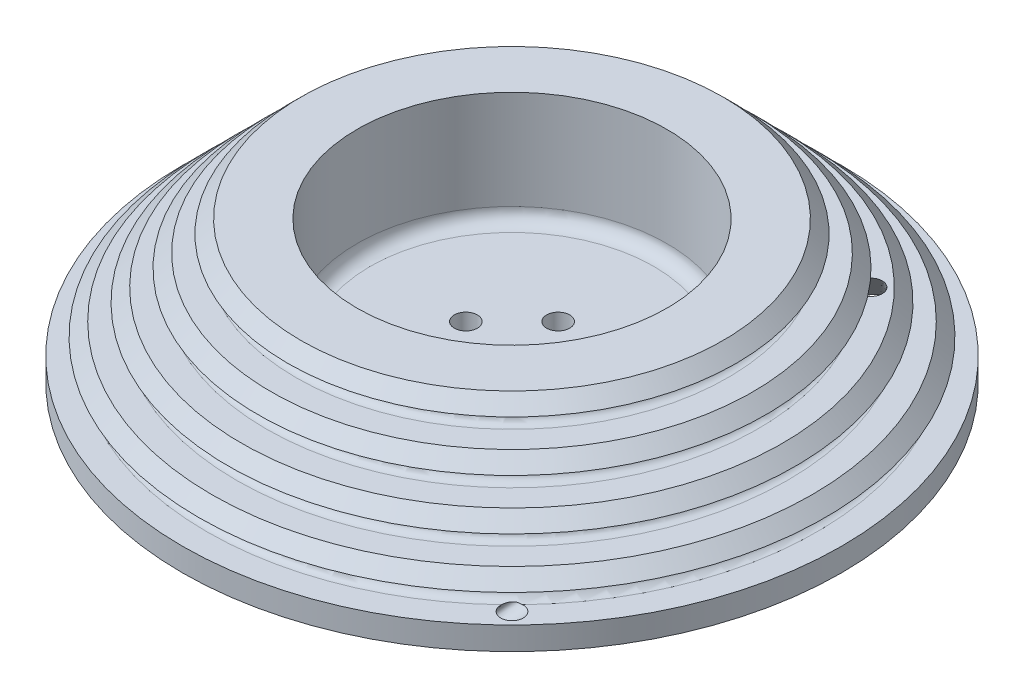
SolidWorks part; units mm, degrees
ref_plane "Front Plane" through (0, 0, 0) normal (0, 0, 1) x (1, 0, 0)
ref_plane "Top Plane" through (0, 0, 0) normal (0, 1, 0) x (1, 0, 0)
ref_plane "Right Plane" through (0, 0, 0) normal (1, 0, 0) x (0, 0, -1)
sketch "Sketch1" plane through (0, 0, 0) normal (0, 0, 1) x (1, 0, 0)
  line L0 (0, 0) -> (0, 21)
  line L1 (0, 21) -> (-32, 21)
  line L2 (-32, 21) -> (-50, 3)
  line L3 (-50, 3) -> (-50, 0)
  line L4 (-50, 0) -> (0, 0)
  dimension "D1" = 50
  dimension "D2" = 21
  dimension "D3" = 135
  dimension "D4" = 3
revolve "Revolve1" add sketch "Sketch1" angle 360 about L0
sketch "Sketch2" plane through (0, 0, 0) normal (0, 0, 1) x (1, 0, 0)
  line L0 (0, 0) -> (0, 23.1188)
  line L1 (-32, 21) -> (-50, 3) construction
  line L2 (-36.5, 19) -> (-31.5, 19)
  line L3 (-36.5, 19) -> (-36.5, 16.5)
  line L4 (-36.5, 16.5) -> (-31.5, 16.5)
  line L5 (-31.5, 19) -> (-31.5, 16.5)
  line L6 (-50, 5.5) -> (-45, 5.5)
  line L7 (-50, 5.5) -> (-50, 3)
  line L8 (-50, 3) -> (-45, 3)
  line L9 (-45, 5.5) -> (-45, 3)
  line L10 (-32, 21) -> (-50, 3)
  line L12 (32, 21) -> (-32, 21) construction
  line L13 (50, 3) -> (-50, 3) construction
  line L15 (-41, 14.5) -> (-36, 14.5)
  line L16 (-41, 14.5) -> (-41, 12)
  line L17 (-41, 12) -> (-36, 12)
  line L18 (-36, 14.5) -> (-36, 12)
  line L19 (-45.5, 10) -> (-40.5, 10)
  line L20 (-45.5, 10) -> (-45.5, 7.5)
  line L21 (-45.5, 7.5) -> (-40.5, 7.5)
  line L22 (-40.5, 10) -> (-40.5, 7.5)
  point P19 (-38.5, 14.5)
  point P26 (-43, 10)
  point P27 (-47.5, 5.5)
  point P28 (-34, 19)
  dimension "D1" = 2.5
  dimension "D2" = 2.5
  dimension "D3" = 5
  dimension "D4" = 5
  dimension "D5" = 5
  dimension "D6" = 2
  dimension "D7" = 2.5
  dimension "D8" = 2
  dimension "D9" = 5
  dimension "D10" = 2.5
  dimension "D11" = 2
revolve "Cut-Revolve1" cut sketch "Sketch2" angle 360 about L0 region at (-46.9444, 4.1111, 0) region at (-42.4444, 8.6111, 0) region at (-37.9444, 13.1111, 0) region at (-33.4444, 17.6111, 0)
fillet "Fillet1" radius 1.25 8 edges at (0, 3, -45) (0, 5.5, -45) (0, 7.5, -40.5) (0, 10, -40.5) (0, 12, -36) (0, 14.5, -36) (0, 16.5, -31.5) (0, 19, -31.5)
sketch "Sketch3" plane through (0, 21, 0) normal (0, 1, 0) x (1, 0, 0)
  line L0 (0, 0) -> (44.738, 0) construction
  line L1 (0, 0) -> (32.1015, 32.1015)
  line L2 (0, 0) -> (32.1015, -32.1015)
  dimension "D1" = 45
ref_plane "top inner hole" through (0, 0, 0) normal (0.7071, 0, 0.7071) x (0.7071, 0, -0.7071)
ref_plane "bottom outer hole" through (0, 0, 0) normal (-0.7071, 0, 0.7071) x (0.7071, 0, 0.7071)
sketch "Sketch5" plane through (0, 0, 0) normal (0.7071, 0, 0.7071) x (0.7071, 0, -0.7071)
  line L0 (36.6973, 7.047) -> (34.1324, 0)
  line L1 (-50, 0) -> (50, 0) construction
  line L2 (41, 12) -> (-41, 12) construction
  line L3 (36.6973, 7.047) -> (38.8222, 12.8851)
  point P4 (38.5, 12)
  dimension "D1" = 2.5
  dimension "D2" = 70
sketch "Sketch6" plane through (0, 0, 0) normal (-0.7071, 0, 0.7071) x (0.7071, 0, 0.7071)
  line L0 (47.5, 3) -> (42.3038, 0)
  line L1 (50, 3) -> (-50, 3) construction
  line L2 (-50, 0) -> (50, 0) construction
  line L3 (47.5, 3) -> (33.9789, -4.8064)
  line L4 (47.5, 3) -> (50.8539, 4.9364)
  dimension "D1" = 2.5
  dimension "D2" = 30
sketch "Sketch11" plane through (0, 21, 0) normal (0, 1, 0) x (1, 0, 0)
  circle A0 centre (0, 0) radius 23.5
  dimension "D1" = 47
extrude "Cut-Extrude2" cut sketch "Sketch11" against normal blind 17
fillet "Fillet2" radius 2 1 edges at (0, 4, 23.5)
ref_plane "Plane1" through (0, 0, 0) normal (0, 0, -1) x (1, 0, 0)
ref_plane "Plane2" through (21.3119, -10.9699, -21.3119) normal (0.6645, -0.342, -0.6645) x (0.2418, 0.9397, -0.2418)
ref_plane "Plane3" through (7.4783, -18.3181, 7.4783) normal (-0.3536, 0.866, -0.3536) x (-0.6124, -0.5, -0.6124)
sketch "Sketch19" plane through (0, 0, 0) normal (0, -1, 0) x (1, 0, 0)
  circle A1 centre (0, 0) radius 50
  circle A2 centre (0, 0) radius 50
  dimension "D1" = 0
extrude "Boss-Extrude1" add sketch "Sketch19" along normal blind 0.5
sketch "Sketch9" plane through (0, -0.5, 0) normal (0, -1, 0) x (1, 0, 0)
  line L0 (0, 0) -> (0, 20.7323)
  line L1 (0, 0) -> (44.738, 0) construction
  circle A0 centre (0, 0) radius 7 construction
  circle A1 centre (0, 7) radius 1.75
  circle A2 centre (7, 0) radius 1.75
  circle A3 centre (0, -7) radius 1.75
  circle A4 centre (-7, 0) radius 1.75
  point P0 (0, 0)
  point P16 (0, 0)
  dimension "D1" = 14
  dimension "D2" = 3.5
  dimension "D3" = 4
extrude "Cut-Extrude1" cut sketch "Sketch9" against normal through all and the other way blind 0.5 contours A4 | L0 A1 | L0 A1 | A2 | A3 region at (-0.7427, -0.5, 7) region at (0.7427, -0.5, 7) region at (7, -0.5, 0) region at (0, -0.5, -7) region at (-7, -0.5, 0)
sketch "Sketch20" plane through (0, -0.5, 0) normal (0, -1, 0) x (1, 0, 0)
  circle A0 centre (0, 0) radius 2.6
  dimension "D1" = 5.2
extrude "Cut-Extrude3" cut sketch "Sketch20" against normal blind 3
sketch "Sketch8" plane through (0, 3, 0) normal (0, 1, 0) x (1, 0, 0)
  circle A0 centre (33.5876, -33.5876) radius 1.7
  dimension "D1" = 3.4
sketch "Sketch7" plane through (0, 12, 0) normal (0, 1, 0) x (1, 0, 0)
  circle A0 centre (27.2236, 27.2236) radius 1.7
  dimension "D1" = 3.4
sketch "Sketch22" plane through (0, 21, 0) normal (0, 1, 0) x (1, 0, 0)
  line L0 (28.4257, 28.4257) -> (51.9261, 4.9253)
  line L2 (27.2236, 27.2236) -> (28.4257, 28.4257)
  line L3 (25.9489, 25.9489) -> (27.4514, 27.4514) construction
  line L4 (34.7897, -34.7897) -> (57.5245, -12.0548)
  line L5 (33.5876, -33.5876) -> (35.9592, -35.9592) construction
  line L6 (27.2236, 27.2236) -> (28.3989, 25.9953)
  line L7 (33.5876, -33.5876) -> (34.7897, -32.3855)
  circle A0 centre (27.2236, 27.2236) radius 1.7 construction
  circle A1 centre (33.5876, -33.5876) radius 1.7 construction
  circle A2 centre (0, 0) radius 38.5 construction
ref_plane "Plane7" through (27.8112, 0, -26.6094) normal (-0.7225, 0, 0.6913) x (0.6913, 0, 0.7225)
ref_plane "Plane8" through (33.5876, 0, 33.5876) normal (0.7071, 0, 0.7071) x (0.7071, 0, -0.7071)
sketch "Sketch24" plane through (27.8112, 0, -26.6094) normal (-0.7225, 0, 0.6913) x (0.6913, 0, 0.7225)
  line L0 (-16.5385, -1.3805) -> (1.161, 13.7152)
  line L2 (-0.8102, 7.047) -> (-0.8571, 12.8851) construction
  point P2 (-14.3017, -2.5124)
  point P3 (1.1241, 13.7795)
  point P5 (-14.6316, -3.3373)
  dimension "D1" = 50
sketch "Sketch25" plane through (33.5876, 0, 33.5876) normal (0.7071, 0, 0.7071) x (0.7071, 0, -0.7071)
  line L0 (1.4897, 4.25) -> (-7.9976, -3.7108)
  line L1 (0, 3) -> (0, -4.8064) construction
  line L2 (0, 3) -> (0, 4.9364) construction
  line L3 (1.7, 3) -> (-1.7, 3) construction
  line L4 (-45, 4.25) -> (45, 4.25) construction
  point P2 (0, 3)
  point P3 (-4.6026, -6.8398)
  point P10 (1.0907, 4.25)
  dimension "D1" = 50
sweep "Cut-Sweep1" cut profiles "Sketch8" path "Sketch25"
sweep "Cut-Sweep2" cut profiles "Sketch7" path "Sketch24"
